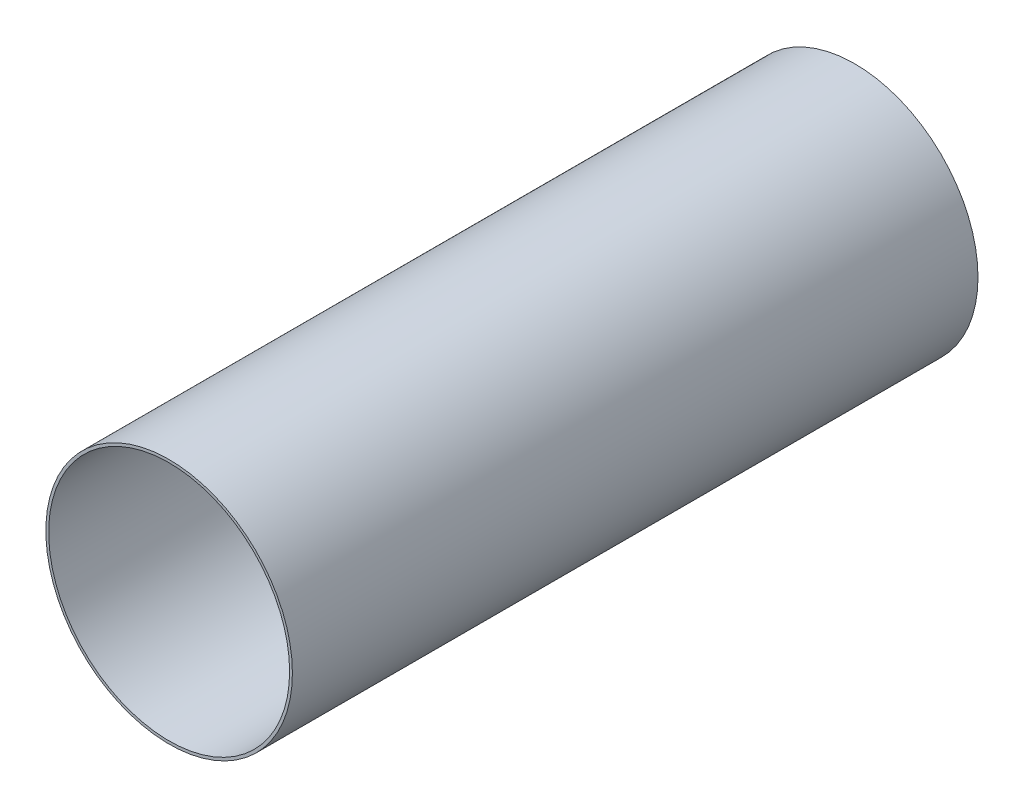
SolidWorks part; units mm, degrees
material "E-Glass Fiber"
ref_plane "Front Plane" through (0, 0, 0) normal (0, 0, 1) x (1, 0, 0)
ref_plane "Top Plane" through (0, 0, 0) normal (0, 1, 0) x (1, 0, 0)
ref_plane "Right Plane" through (0, 0, 0) normal (1, 0, 0) x (0, 0, -1)
sketch "Sketch1" plane through (0, 0, 0) normal (0, 0, 1) x (1, 0, 0)
  circle A0 centre (0, 0) radius 49.6697
  circle A1 centre (0, 0) radius 48.5394
  dimension "D1" = 99.3394
  dimension "D2" = 97.0788
extrude "Boss-Extrude1" add sketch "Sketch1" along normal blind 276.225
